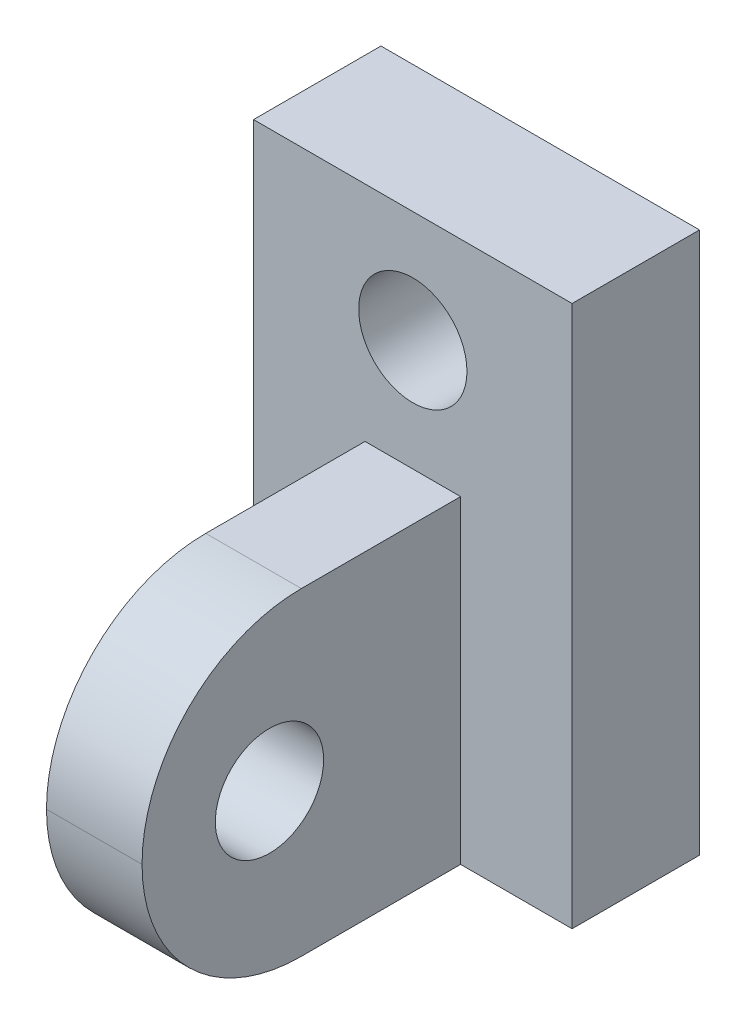
SolidWorks part; units mm, degrees
ref_plane "Front Plane" through (0, 0, 0) normal (0, 0, 1) x (1, 0, 0)
ref_plane "Top Plane" through (0, 0, 0) normal (0, 1, 0) x (1, 0, 0)
ref_plane "Right Plane" through (0, 0, 0) normal (1, 0, 0) x (0, 0, -1)
sketch "Sketch1" plane through (0, 0, 0) normal (0, 0, 1) x (1, 0, 0)
  line L1 (0, 0) -> (10, 0)
  line L2 (0, 0) -> (0, 15)
  line L3 (0, 15) -> (10, 15)
  line L4 (10, 0) -> (10, 15)
  line L5 (3.2418, 10) -> (6.2418, 10)
  line L6 (3.2418, 10) -> (3.2418, 0)
  line L7 (3.2418, 0) -> (6.2418, 0)
  line L8 (6.2418, 10) -> (6.2418, 0)
  line L9 (3.2418, 10) -> (6.2418, 0) construction
  line L10 (3.2418, 0) -> (6.2418, 10) construction
  point P5 (4.7418, 5)
  dimension "D1" = 15
  dimension "D2" = 10
  dimension "D3" = 3
  dimension "D4" = 10
extrude "Boss-Extrude1" add sketch "Sketch1" along normal blind 4 contours L5 L8 L1 L4 L3 L2 L6 | L8 L5 L6 L1 region at (0.1803, 7.5, 0) region at (4.7418, 5, 0)
sketch "Sketch2" plane through (0, 0, 4) normal (0, 0, 1) x (1, 0, 0)
  line L0 (0, 0) -> (10, 0) construction
  line L1 (3.5, 10) -> (6.5, 10)
  line L2 (3.5, 10) -> (3.5, 0)
  line L3 (3.5, 0) -> (6.5, 0)
  line L4 (6.5, 10) -> (6.5, 0)
  line L5 (3.5, 10) -> (6.5, 0) construction
  line L6 (3.5, 0) -> (6.5, 10) construction
  line L7 (10, 0) -> (10, 15) construction
  point P0 (5, 5)
  dimension "D1" = 10
  dimension "D2" = 3
  dimension "D3" = 5
extrude "Boss-Extrude2" add sketch "Sketch2" along normal blind 10
fillet "Fillet1" radius 5 2 edges at (5, 0, 14) (5, 10, 14)
hole_wizard "M3 Clearance Hole1" positions "Sketch4" profile "Sketch3" hole size "M3" standard "ANSI Metric"
sketch "Sketch4" plane through (0, 0, 4) normal (0, 0, 1) x (1, 0, 0)
  line L0 (0, 15) -> (10, 15) construction
  line L1 (0, 0) -> (0, 15) construction
  point P0 (5, 13.5)
  point P7 (12.5477, 14.0559)
  dimension "D1" = 1.5
  dimension "D2" = 5
sketch "Sketch3" plane through (5, 13.5, 4) normal (1, 0, 0) x (0, -1, 0)
  line L0 (0, 0) -> (0, 71.0215)
  line L1 (0, 71.0215) -> (1.7, 70)
  line L2 (1.7, 70) -> (1.7, 0)
  line L5 (1.7, 0) -> (0, 0)
  line L10 (0, 71.0215) -> (-1.7, 70) construction
  line L11 (0, -6.35) -> (0, 107.95) construction
  dimension "Hole Dia." = 3.4
  dimension "Hole Depth" = 70
  dimension "Drill Angle" = 118
sketch "Sketch6" plane through (0, 15, 0) normal (0, 1, 0) x (1, 0, 0)
  line L2 (0, -4) -> (10, -4)
  line L3 (0, -4) -> (0, 0)
  line L4 (0, 0) -> (10, 0)
  line L5 (10, -4) -> (10, 0)
extrude "Boss-Extrude3" add sketch "Sketch6" along normal blind 2
hole_wizard "M3 Clearance Hole2" positions "Sketch11" profile "Sketch10" hole size "M3" standard "ANSI Metric"
sketch "Sketch11" plane through (0, 0, 4) normal (0, 0, 1) x (1, 0, 0)
  point P0 (5, 13.5)
sketch "Sketch10" plane through (5, 13.5, 4) normal (1, 0, 0) x (0, -1, 0)
  line L0 (0, 0) -> (0, 71.0215)
  line L1 (0, 71.0215) -> (1.7, 70)
  line L2 (1.7, 70) -> (1.7, 0)
  line L5 (1.7, 0) -> (0, 0)
  line L10 (0, 71.0215) -> (-1.7, 70) construction
  line L11 (0, -6.35) -> (0, 107.95) construction
  dimension "Hole Dia." = 3.4
  dimension "Hole Depth" = 70
  dimension "Drill Angle" = 118
hole_wizard "M3 Clearance Hole3" positions "Sketch13" profile "Sketch12" hole size "M3" standard "ANSI Metric"
sketch "Sketch13" plane through (6.5, 0, 0) normal (1, 0, 0) x (0, 0, -1)
  line L0 (-9, 0) -> (-4, 0) construction
  point P0 (-10, 5)
  dimension "D1" = 4
  dimension "D2" = 5
sketch "Sketch12" plane through (6.5, 5, 10) normal (0, 1, 0) x (0, 0, -1)
  line L0 (0, 0) -> (0, 71.0215)
  line L1 (0, 71.0215) -> (1.7, 70)
  line L2 (1.7, 70) -> (1.7, 0)
  line L5 (1.7, 0) -> (0, 0)
  line L10 (0, 71.0215) -> (-1.7, 70) construction
  line L11 (0, -6.35) -> (0, 107.95) construction
  dimension "Hole Dia." = 3.4
  dimension "Hole Depth" = 70
  dimension "Drill Angle" = 118
